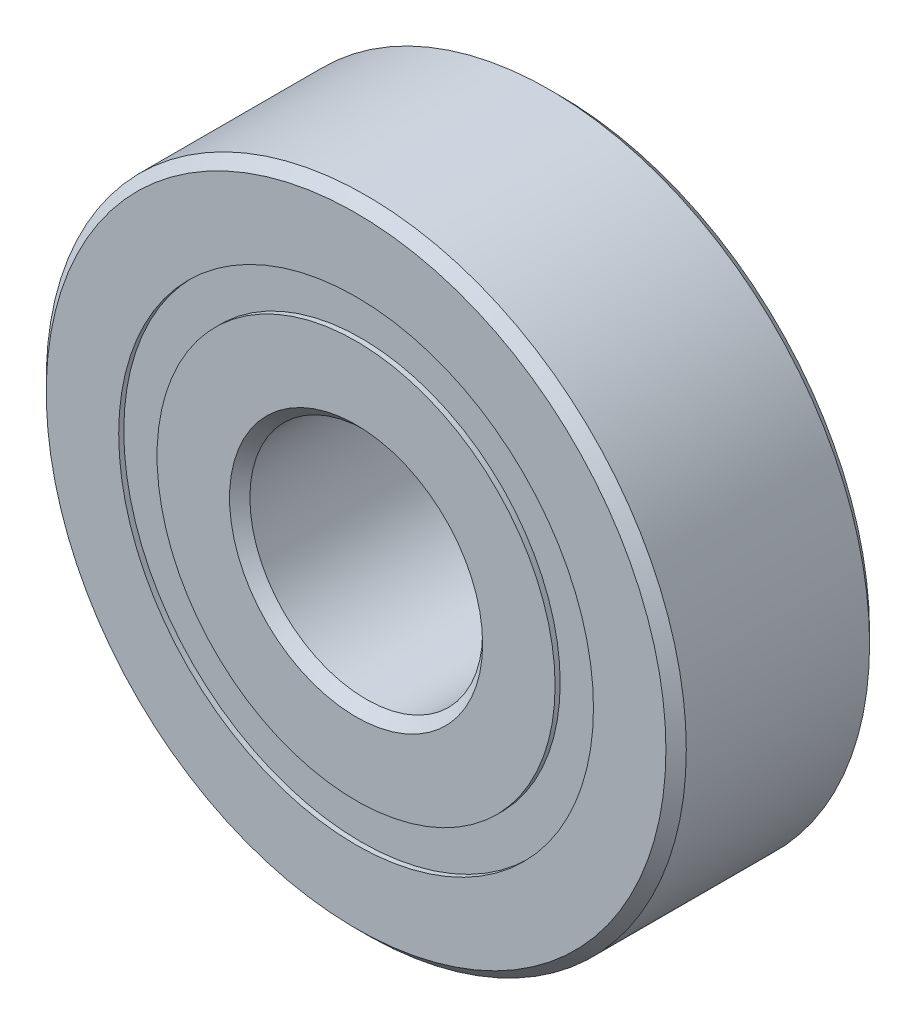
SolidWorks part; units mm, degrees
ref_plane "Front Plane" through (0, 0, 0) normal (0, 0, 1) x (1, 0, 0)
ref_plane "Top Plane" through (0, 0, 0) normal (0, 1, 0) x (1, 0, 0)
ref_plane "Right Plane" through (0, 0, 0) normal (1, 0, 0) x (0, 0, -1)
sketch "Sketch1" plane through (0, 0, 0) normal (1, 0, 0) x (0, 0, -1)
  line L0 (-3.5, 0) -> (3.5, 0) construction
  line L1 (0, 11) -> (0, -11) construction
  line L2 (3.15, 11) -> (-3.15, 11)
  line L3 (-3.15, 11) -> (-3.5, 10.65)
  line L4 (-3.5, 10.65) -> (-3.5, 8.1593)
  line L5 (-3.5, 8.1593) -> (-1.5556, 8.1593)
  line L6 (3.5, 8.1593) -> (1.5556, 8.1593)
  line L7 (3.5, 10.65) -> (3.5, 8.1593)
  line L8 (3.15, 11) -> (3.5, 10.65)
  line L9 (0, 11) -> (0, 7.5) construction
  line L10 (0, 7.5) -> (0, 4) construction
  arc A0 (-1.5556, 8.1593) -> (1.5556, 8.1593) centre (0, 7.5) cw
  point P14 (0, 4)
  point P15 (0, 0)
  dimension "D3" = 3.1111
  dimension "D1" = 45
  dimension "Width" = 7
  dimension "OD" = 22
  dimension "D2" = 0.35
  dimension "Shaft Dia" = 8
  dimension "D4" = 0.6593
revolve "Revolve1" add sketch "Sketch1" angle 360 about L0
sketch "Sketch3" plane through (0, 0, 0) normal (1, 0, 0) x (0, 0, -1)
  line L0 (-3.5, 6.8407) -> (-1.5556, 6.8407)
  line L1 (0, 11) -> (0, -11) construction
  line L2 (-3.5, 10.65) -> (-3.5, 8.1593) construction
  line L3 (-3.5, 6.8407) -> (-3.5, 4.35)
  line L4 (-3.15, 11) -> (-3.5, 10.65) construction
  line L5 (-3.5, 4.35) -> (-3.15, 4)
  line L6 (-3.15, 4) -> (3.15, 4)
  line L7 (3.15, 11) -> (3.15, -11) construction
  line L8 (3.15, 4) -> (3.5, 4.35)
  line L9 (3.5, -10.65) -> (3.5, 10.65) construction
  line L10 (3.5, 4.35) -> (3.5, 6.8407)
  line L11 (3.5, 6.8407) -> (1.5556, 6.8407)
  line L13 (3.15, 11) -> (3.5, 10.65) construction
  arc A0 (1.5556, 8.1593) -> (-1.5556, 8.1593) centre (0, 7.5) ccw construction
  arc A1 (1.5556, 6.8407) -> (-1.5556, 6.8407) centre (0, 7.5) cw
revolve "Revolve3" add sketch "Sketch3" angle 360 about L0
sketch "Sketch4" plane through (0, 0, 0) normal (1, 0, 0) x (0, 0, -1)
  line L0 (-1.6895, 7.5) -> (1.6895, 7.5)
  arc A2 (-1.6895, 7.5) -> (1.6895, 7.5) centre (0, 7.5) cw
  arc A3 (1.5556, 8.1593) -> (-1.5556, 8.1593) centre (0, 7.5) ccw construction
revolve "Revolve4" add sketch "Sketch4" angle 360 about L0
ref_axis "Axis1" through (0, 0, -3.5) along (0, 0, 1)
pattern_circular "CirPattern1" count 12 every 30 about axis through (0, 0, -3.5) along (0, 0, 1) of bodies 104
sketch "Sketch5" plane through (0, 0, 0) normal (1, 0, 0) x (0, 0, -1)
  line L0 (-3.5, 8.1593) -> (-1.5556, 8.1593) construction
  line L1 (-3.325, 8.1593) -> (-1.6895, 8.1593)
  line L2 (-3.325, 8.1593) -> (-3.325, 6.8407)
  line L3 (-3.325, 6.8407) -> (-1.6895, 6.8407)
  line L4 (-1.6895, 8.1593) -> (-1.6895, 6.8407)
  line L5 (-3.5, 6.8407) -> (-1.5556, 6.8407) construction
  line L6 (3.5, 8.1593) -> (1.5556, 8.1593) construction
  line L7 (3.325, 8.1593) -> (1.6895, 8.1593)
  line L8 (3.325, 8.1593) -> (3.325, 6.8407)
  line L9 (3.325, 6.8407) -> (1.6895, 6.8407)
  line L10 (1.6895, 8.1593) -> (1.6895, 6.8407)
  line L11 (3.5, 6.8407) -> (1.5556, 6.8407) construction
  line L12 (-3.15, 11) -> (-3.5, 10.65) construction
  point P18 (-3.325, 10.825)
revolve "Revolve5" add sketch "Sketch5" angle 360 about L0
equation "\"D2@Sketch1\" = \"Width@Sketch1\"*.05"
equation "\"D3@Sketch1\" = \"Width@Sketch1\"/2.25"
equation "\"D4@Sketch1\" = (((\"OD@Sketch1\"-\"Width@Sketch1\")/2)/3.25)/3.5"
equation "\"D2@CirPattern1\" = 360/\"Balls@CirPattern1\""
